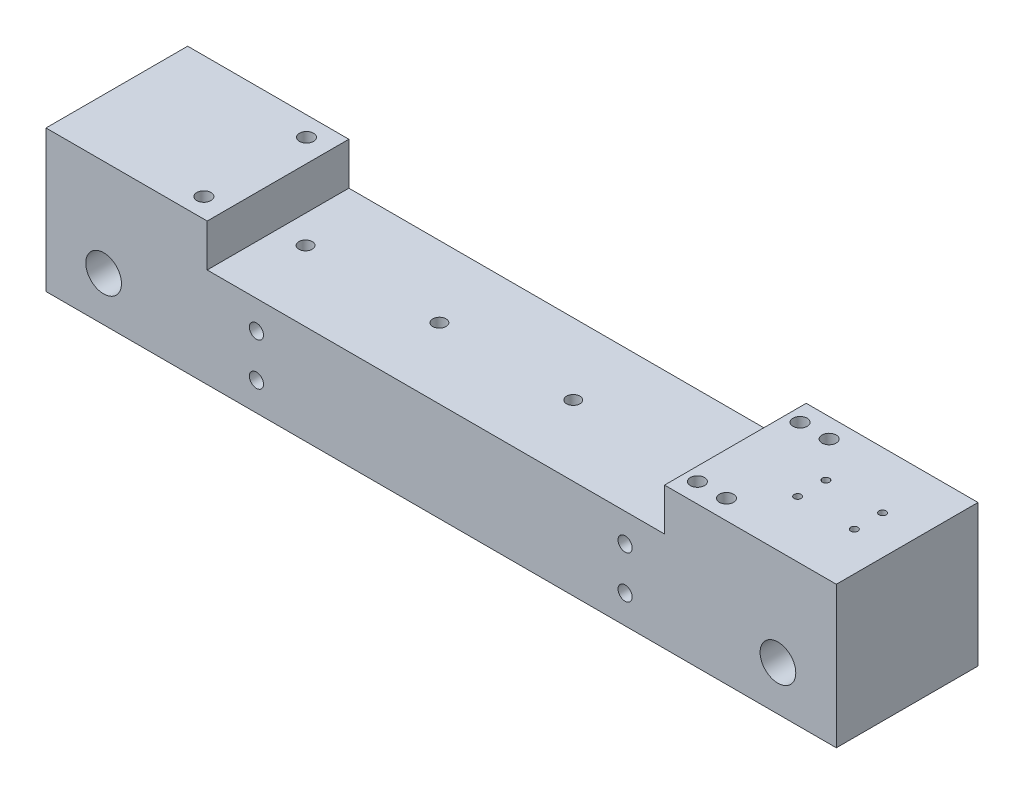
SolidWorks part; units mm, degrees
material "McMaster Steel"
ref_plane "Front Plane" through (0, 0, 0) normal (0, 0, 1) x (1, 0, 0)
ref_plane "Top Plane" through (0, 0, 0) normal (0, 1, 0) x (1, 0, 0)
ref_plane "Right Plane" through (0, 0, 0) normal (1, 0, 0) x (0, 0, -1)
sketch "Sketch1" plane through (0, 0, 0) normal (0, 0, 1) x (1, 0, 0)
  line L0 (177.125, 59) -> (177.125, 63.5)
  line L1 (177.125, 63.5) -> (100.125, 63.5)
  line L2 (100.125, 63.5) -> (100.125, 59)
  line L3 (100.125, 44.5) -> (-104.875, 44.5)
  line L4 (-2.375, 44.5) -> (-2.375, 40)
  line L5 (-104.875, 63.5) -> (-177.125, 63.5)
  line L6 (-177.125, 63.5) -> (-177.125, 59)
  line L7 (-104.875, 63.5) -> (-104.875, 59)
  circle A0 centre (164.385, 33.435) radius 2.6035
  circle A1 centre (169.95, 20) radius 2.6035
  circle A2 centre (164.385, 6.565) radius 2.6035
  circle A3 centre (137.515, 6.565) radius 2.6035
  circle A4 centre (131.95, 20) radius 2.6035
  circle A5 centre (137.515, 33.435) radius 2.6035
  circle A6 centre (-137.865, 33.435) radius 2.6035
  circle A7 centre (-132.3, 20) radius 2.6035
  circle A8 centre (-137.865, 6.565) radius 2.6035
  circle A9 centre (-164.735, 6.565) radius 2.6035
  circle A10 centre (-170.3, 20) radius 2.6035
  circle A11 centre (-164.735, 33.435) radius 2.6035
  line B0 (-177.125, 0) -> (177.125, 0)
  line B1 (177.125, 0) -> (177.125, 59)
  line B2 (177.125, 59) -> (100.125, 59)
  line B3 (100.125, 59) -> (100.125, 40)
  line B4 (100.125, 40) -> (-104.875, 40)
  line B5 (-104.875, 40) -> (-104.875, 59)
  line B6 (-104.875, 59) -> (-177.125, 59)
  line B7 (-177.125, 59) -> (-177.125, 0)
  circle B8 centre (-151.3, 20) radius 14
  circle B9 centre (150.95, 20) radius 14
  arc B10 (-164.735, 9.315) -> (-164.735, 3.815) centre (-164.735, 6.565) ccw
  arc B11 (-164.735, 9.315) -> (-164.735, 3.815) centre (-164.735, 6.565) ccw
  arc B12 (-164.735, 3.815) -> (-164.735, 9.315) centre (-164.735, 6.565) ccw
  arc B13 (-164.735, 3.815) -> (-164.735, 9.315) centre (-164.735, 6.565) ccw
  arc B14 (-137.865, 3.815) -> (-137.865, 9.315) centre (-137.865, 6.565) ccw
  arc B15 (-137.865, 3.815) -> (-137.865, 9.315) centre (-137.865, 6.565) ccw
  arc B16 (-137.865, 9.315) -> (-137.865, 3.815) centre (-137.865, 6.565) ccw
  arc B17 (-137.865, 9.315) -> (-137.865, 3.815) centre (-137.865, 6.565) ccw
  arc B18 (-132.3, 17.25) -> (-132.3, 22.75) centre (-132.3, 20) ccw
  arc B19 (-132.3, 17.25) -> (-132.3, 22.75) centre (-132.3, 20) ccw
  arc B20 (-132.3, 22.75) -> (-132.3, 17.25) centre (-132.3, 20) ccw
  arc B21 (-132.3, 22.75) -> (-132.3, 17.25) centre (-132.3, 20) ccw
  arc B22 (-137.865, 30.685) -> (-137.865, 36.185) centre (-137.865, 33.435) ccw
  arc B23 (-137.865, 30.685) -> (-137.865, 36.185) centre (-137.865, 33.435) ccw
  arc B24 (-137.865, 36.185) -> (-137.865, 30.685) centre (-137.865, 33.435) ccw
  arc B25 (-137.865, 36.185) -> (-137.865, 30.685) centre (-137.865, 33.435) ccw
  arc B26 (-170.3, 17.25) -> (-170.3, 22.75) centre (-170.3, 20) ccw
  arc B27 (-170.3, 17.25) -> (-170.3, 22.75) centre (-170.3, 20) ccw
  arc B28 (-170.3, 22.75) -> (-170.3, 17.25) centre (-170.3, 20) ccw
  arc B29 (-170.3, 22.75) -> (-170.3, 17.25) centre (-170.3, 20) ccw
  arc B30 (-164.735, 30.685) -> (-164.735, 36.185) centre (-164.735, 33.435) ccw
  arc B31 (-164.735, 30.685) -> (-164.735, 36.185) centre (-164.735, 33.435) ccw
  arc B32 (-164.735, 36.185) -> (-164.735, 30.685) centre (-164.735, 33.435) ccw
  arc B33 (-164.735, 36.185) -> (-164.735, 30.685) centre (-164.735, 33.435) ccw
  arc B34 (137.515, 9.315) -> (137.515, 3.815) centre (137.515, 6.565) ccw
  arc B35 (137.515, 9.315) -> (137.515, 3.815) centre (137.515, 6.565) ccw
  arc B36 (137.515, 3.815) -> (137.515, 9.315) centre (137.515, 6.565) ccw
  arc B37 (137.515, 3.815) -> (137.515, 9.315) centre (137.515, 6.565) ccw
  arc B38 (164.385, 9.315) -> (164.385, 3.815) centre (164.385, 6.565) ccw
  arc B39 (164.385, 9.315) -> (164.385, 3.815) centre (164.385, 6.565) ccw
  arc B40 (164.385, 3.815) -> (164.385, 9.315) centre (164.385, 6.565) ccw
  arc B41 (164.385, 3.815) -> (164.385, 9.315) centre (164.385, 6.565) ccw
  arc B42 (169.95, 17.25) -> (169.95, 22.75) centre (169.95, 20) ccw
  arc B43 (169.95, 17.25) -> (169.95, 22.75) centre (169.95, 20) ccw
  arc B44 (169.95, 22.75) -> (169.95, 17.25) centre (169.95, 20) ccw
  arc B45 (169.95, 22.75) -> (169.95, 17.25) centre (169.95, 20) ccw
  arc B46 (164.385, 30.685) -> (164.385, 36.185) centre (164.385, 33.435) ccw
  arc B47 (164.385, 30.685) -> (164.385, 36.185) centre (164.385, 33.435) ccw
  arc B48 (164.385, 36.185) -> (164.385, 30.685) centre (164.385, 33.435) ccw
  arc B49 (164.385, 36.185) -> (164.385, 30.685) centre (164.385, 33.435) ccw
  arc B50 (131.95, 17.25) -> (131.95, 22.75) centre (131.95, 20) ccw
  arc B51 (131.95, 17.25) -> (131.95, 22.75) centre (131.95, 20) ccw
  arc B52 (131.95, 22.75) -> (131.95, 17.25) centre (131.95, 20) ccw
  arc B53 (131.95, 22.75) -> (131.95, 17.25) centre (131.95, 20) ccw
  arc B54 (137.515, 30.685) -> (137.515, 36.185) centre (137.515, 33.435) ccw
  arc B55 (137.515, 30.685) -> (137.515, 36.185) centre (137.515, 33.435) ccw
  arc B56 (137.515, 36.185) -> (137.515, 30.685) centre (137.515, 33.435) ccw
  arc B57 (137.515, 36.185) -> (137.515, 30.685) centre (137.515, 33.435) ccw
  dimension "D1" = 5.207
  dimension "D2" = 63.5
sketch_block_instance "Block-SecondaryBlock Sideview-1"
sketch_block "Block-SecondaryBlock Sideview"
extrude "Boss-Extrude1" add sketch "Sketch1" along normal blind 63.5 contours B6 B7 B0 B1 B2 B3 B4 B5 B56 B54 B52 B50 B48 B46 B44 B42 B40 B38 B36 B34 B32 B30 B28 B26 B24 B22 B20 B18 B16 B14 B12 B10 B9 B8 | B46 B48 A0 | B54 B56 A5 | B42 B44 A1 | B38 B40 A2 | B50 B52 A4 | B34 B36 A3 | B22 B24 A6 | B18 B20 A7 | B14 B16 A8 | B10 B12 A9 | B26 B28 A10 | B30 B32 A11 | B2 L0 L1 L2 | B4 B3 L3 L4 | B6 L7 L5 L6 | B5 B4 L4 L3 region at (138.625, 61.25, 0) region at (0.6144, 25.4009, 0) region at (48.875, 42.25, 0) region at (-141, 61.25, 0) region at (-53.625, 42.25, 0) region at (-162.0628, 6.565, 0) region at (-140.5372, 6.565, 0) region at (-134.9722, 20, 0) region at (-140.5372, 33.435, 0) region at (-172.9722, 20, 0) region at (-167.4072, 33.435, 0) region at (140.1872, 6.565, 0) region at (167.0572, 6.565, 0) region at (167.2778, 20, 0) region at (161.7128, 33.435, 0) region at (129.2778, 20, 0) region at (134.8428, 33.435, 0)
sketch "Sketch2" plane through (0, 63.5, 0) normal (0, 1, 0) x (1, 0, 0)
  line L0 (177.125, -61.75) -> (177.125, -1.75)
  line L2 (177.125, -63.5) -> (177.125, 0) construction
  circle A0 centre (119.125, -54.75) radius 3.175
  circle A1 centre (106.125, -54.75) radius 3.175
  circle A2 centre (119.125, -8.75) radius 3.175
  circle A3 centre (106.125, -8.75) radius 3.175
  circle A4 centre (-115.125, -54.75) radius 3.175
  circle A5 centre (-115.125, -8.75) radius 3.175
  point P13 (177.125, -31.75)
  point P20 (177.125, -31.75)
  line B0 (-177.125, -1.75) -> (177.125, -1.75)
  line B1 (177.125, -1.75) -> (177.125, -41.55)
  line B2 (177.125, -41.55) -> (-177.125, -41.55) construction
  line B3 (-177.125, -41.55) -> (-177.125, -1.75)
  line B4 (-177.125, -41.55) -> (-177.125, -61.75)
  line B5 (-177.125, -61.75) -> (177.125, -61.75)
  line B6 (177.125, -61.75) -> (177.125, -41.55)
  arc B7 (-118.425, -8.75) -> (-111.825, -8.75) centre (-115.125, -8.75) ccw
  arc B8 (-111.825, -8.75) -> (-118.425, -8.75) centre (-115.125, -8.75) ccw
  arc B9 (-118.425, -54.75) -> (-111.825, -54.75) centre (-115.125, -54.75) ccw
  arc B10 (-111.825, -54.75) -> (-118.425, -54.75) centre (-115.125, -54.75) ccw
  arc B11 (-132.725, -34.65) -> (-128.525, -34.65) centre (-130.625, -34.65) ccw
  arc B12 (-128.525, -34.65) -> (-132.725, -34.65) centre (-130.625, -34.65) ccw
  arc B13 (-132.725, -8.65) -> (-128.525, -8.65) centre (-130.625, -8.65) ccw
  arc B14 (-128.525, -8.65) -> (-132.725, -8.65) centre (-130.625, -8.65) ccw
  arc B15 (-173.725, -34.65) -> (-169.525, -34.65) centre (-171.625, -34.65) ccw
  arc B16 (-169.525, -34.65) -> (-173.725, -34.65) centre (-171.625, -34.65) ccw
  arc B17 (-173.725, -8.65) -> (-169.525, -8.65) centre (-171.625, -8.65) ccw
  arc B18 (-169.525, -8.65) -> (-173.725, -8.65) centre (-171.625, -8.65) ccw
  arc B19 (128.525, -8.65) -> (132.725, -8.65) centre (130.625, -8.65) ccw
  arc B20 (132.725, -8.65) -> (128.525, -8.65) centre (130.625, -8.65) ccw
  arc B21 (169.525, -8.65) -> (173.725, -8.65) centre (171.625, -8.65) ccw
  arc B22 (173.725, -8.65) -> (169.525, -8.65) centre (171.625, -8.65) ccw
  arc B23 (169.525, -34.65) -> (173.725, -34.65) centre (171.625, -34.65) ccw
  arc B24 (173.725, -34.65) -> (169.525, -34.65) centre (171.625, -34.65) ccw
  arc B25 (128.525, -34.65) -> (132.725, -34.65) centre (130.625, -34.65) ccw
  arc B26 (132.725, -34.65) -> (128.525, -34.65) centre (130.625, -34.65) ccw
  arc B27 (115.825, -54.75) -> (122.425, -54.75) centre (119.125, -54.75) ccw
  arc B28 (122.425, -54.75) -> (115.825, -54.75) centre (119.125, -54.75) ccw
  arc B29 (102.825, -54.75) -> (109.425, -54.75) centre (106.125, -54.75) ccw
  arc B30 (109.425, -54.75) -> (102.825, -54.75) centre (106.125, -54.75) ccw
  arc B31 (115.825, -8.75) -> (122.425, -8.75) centre (119.125, -8.75) ccw
  arc B32 (122.425, -8.75) -> (115.825, -8.75) centre (119.125, -8.75) ccw
  arc B33 (102.825, -8.75) -> (109.425, -8.75) centre (106.125, -8.75) ccw
  arc B34 (109.425, -8.75) -> (102.825, -8.75) centre (106.125, -8.75) ccw
  dimension "D1" = 6.35
sketch_block_instance "Block-SecondaryBlock Topview-1"
sketch_block "Block-SecondaryBlock Topview"
extrude "Cut-Extrude1" cut sketch "Sketch2" against normal blind 19.05 contours A0 | A1 | A2 | A3 | A4 | A5 region at (119.125, 63.5, 54.75) region at (106.125, 63.5, 54.75) region at (119.125, 63.5, 8.75) region at (106.125, 63.5, 8.75) region at (-115.125, 63.5, 54.75) region at (-115.125, 63.5, 8.75)
extrude "Cut-Extrude3" cut sketch "Sketch2<3>" along normal blind 6.35 from surface contours B23 B24 | B25 B26 | B19 B20 | B21 B22 | B11 B12 | B13 B14 | B17 B18 | B15 B16 region at (-130.625, 63.5, 34.65) region at (-130.625, 63.5, 8.65) region at (-171.625, 63.5, 34.65) region at (-171.625, 63.5, 8.65) region at (130.625, 63.5, 8.65) region at (171.625, 63.5, 8.65) region at (171.625, 63.5, 34.65) region at (130.625, 63.5, 34.65) starting at face at (0, 0, 31.75)
sketch "Sketch2<3>" plane through (0, 63.5, 0) normal (0, 1, 0) x (1, 0, 0) same geometry as "Sketch2"
sketch "Sketch3" plane through (0, 0, 0) normal (0, 0, -1) x (-1, 0, 0)
  circle A1 centre (-150.95, 20) radius 8
  circle A3 centre (-150.95, 20) radius 14
  circle A4 centre (-150.95, 20) radius 14 construction
  circle A5 centre (151.3, 20) radius 8
  circle A6 centre (151.3, 20) radius 14
  circle A7 centre (151.3, 20) radius 14 construction
  dimension "D2" = 16
extrude "Boss-Extrude2" add sketch "Sketch3" along normal offset from surface (31.5 mm away) 32 from surface up to face at (164.95, 20, 0) starting at face at (164.95, 20, 63.5)
sketch "Sketch4" plane through (0, 63.5, 0) normal (0, 1, 0) x (1, 0, 0)
  line L0 (177.125, -63.5) -> (177.125, 0) construction
  point P1 (100.125, -31.75)
  point P5 (177.125, -31.75)
  line B0 (177.125, -1.75) -> (100.125, -1.75)
  line B1 (100.125, -1.75) -> (100.125, -61.75)
  line B2 (100.125, -61.75) -> (177.125, -61.75)
  line B3 (177.125, -61.75) -> (177.125, -1.75)
  line B4 (128.025, -22.25) -> (128.025, -41.25) construction
  line B5 (128.025, -22.25) -> (166.125, -22.25) construction
  line B6 (128.025, -41.25) -> (166.125, -41.25) construction
  line B7 (166.125, -22.25) -> (166.125, -41.25) construction
  circle B8 centre (134.375, -38.075) radius 1.5875
  circle B9 centre (134.375, -25.425) radius 1.5875
  circle B10 centre (159.775, -25.425) radius 1.5875
  circle B11 centre (159.775, -38.075) radius 1.5875
sketch_block_instance "Block-MotorMounting TopView 2-1"
sketch_block "Block-MotorMounting TopView 2"
extrude "Cut-Extrude4" cut sketch "Sketch4" against normal blind 6.35 contours B11 | B10 | B9 | B8 region at (134.375, 63.5, 38.075) region at (134.375, 63.5, 25.425) region at (159.775, 63.5, 25.425) region at (159.775, 63.5, 38.075)
sketch "Sketch5" plane through (0, 0, 63.5) normal (0, 0, 1) x (1, 0, 0)
  circle A0 centre (131.95, 20) radius 2.6035 construction
  circle A1 centre (137.515, 6.565) radius 2.6035 construction
  circle A2 centre (164.385, 6.565) radius 2.6035 construction
  circle A3 centre (169.95, 20) radius 2.6035 construction
  circle A4 centre (164.385, 33.435) radius 2.6035 construction
  circle A5 centre (137.515, 33.435) radius 2.6035 construction
  circle A6 centre (-137.865, 6.565) radius 2.6035 construction
  circle A7 centre (-132.3, 20) radius 2.6035 construction
  circle A8 centre (-137.865, 33.435) radius 2.6035 construction
  circle A9 centre (-164.735, 6.565) radius 2.6035 construction
  circle A10 centre (-170.3, 20) radius 2.6035 construction
  circle A11 centre (-164.735, 33.435) radius 2.6035 construction
  circle A12 centre (131.95, 20) radius 2.6035
  circle A13 centre (137.515, 6.565) radius 2.6035
  circle A14 centre (164.385, 6.565) radius 2.6035
  circle A15 centre (169.95, 20) radius 2.6035
  circle A16 centre (164.385, 33.435) radius 2.6035
  circle A17 centre (137.515, 33.435) radius 2.6035
  circle A18 centre (-137.865, 6.565) radius 2.6035
  circle A19 centre (-132.3, 20) radius 2.6035
  circle A20 centre (-137.865, 33.435) radius 2.6035
  circle A21 centre (-164.735, 6.565) radius 2.6035
  circle A22 centre (-170.3, 20) radius 2.6035
  circle A23 centre (-164.735, 33.435) radius 2.6035
extrude "Boss-Extrude3" add sketch "Sketch5" against normal offset from surface (50.8 mm away) 12.7 up to face at (164.95, 20, 0)
sketch "Sketch6" plane through (0, 44.5, 0) normal (0, 1, 0) x (1, 0, 0)
  line B0 (-104.875, -25.8312) -> (-104.875, -38.0188)
  line B1 (-104.875, -38.0188) -> (100.125, -38.0188)
  line B2 (100.125, -38.0188) -> (100.125, -25.8312)
  line B3 (100.125, -25.8312) -> (-104.875, -25.8312)
  line B4 (100.125, 0) -> (-104.875, 0)
  line B5 (-104.875, 0) -> (-104.875, -63.5)
  line B6 (-104.875, -63.5) -> (100.125, -63.5)
  line B7 (100.125, -63.5) -> (100.125, 0)
  arc B8 (27.625, -34.925) -> (27.625, -28.925) centre (27.625, -31.925) ccw
  arc B9 (27.625, -28.925) -> (27.625, -34.925) centre (27.625, -31.925) ccw
  arc B10 (87.625, -34.925) -> (87.625, -28.925) centre (87.625, -31.925) ccw
  arc B11 (87.625, -28.925) -> (87.625, -34.925) centre (87.625, -31.925) ccw
  arc B12 (-32.3698, -34.925) -> (-32.3698, -28.925) centre (-32.3698, -31.925) ccw
  arc B13 (-32.3698, -28.925) -> (-32.3698, -34.925) centre (-32.3698, -31.925) ccw
  arc B14 (-92.3646, -34.925) -> (-92.3646, -28.925) centre (-92.3646, -31.925) ccw
  arc B15 (-92.3646, -28.925) -> (-92.3646, -34.925) centre (-92.3646, -31.925) ccw
sketch_block_instance "Block-CarriageMountingTop-1"
sketch_block "Block-CarriageMountingTop" parameters "D1"=60
extrude "Cut-Extrude5" cut sketch "Sketch6" against normal blind 6.35 contours B10 B11 | B8 B9 | B12 B13 | B14 B15 region at (27.625, 44.5, 31.925) region at (87.625, 44.5, 31.925) region at (-32.3698, 44.5, 31.925) region at (-92.3646, 44.5, 31.925)
fillet "Fillet1" [suppressed] radius 1.27
sketch "Sketch7" plane through (0, 0, 63.5) normal (0, 0, 1) x (1, 0, 0)
  point P0 (-177.125, 0)
  line B0 (-177.125, 0) -> (177.125, 0) construction
  circle B1 centre (-82.8012, 31.8013) radius 3.175
  circle B2 centre (-82.8012, 12.7513) radius 3.175
  circle B3 centre (82.4512, 12.7513) radius 3.175
  circle B4 centre (82.4512, 31.8013) radius 3.175
sketch_block_instance "Block-SensorMountingtoGantry-1"
sketch_block "Block-SensorMountingtoGantry"
extrude "Cut-Extrude6" cut sketch "Sketch7" against normal blind 6.35
